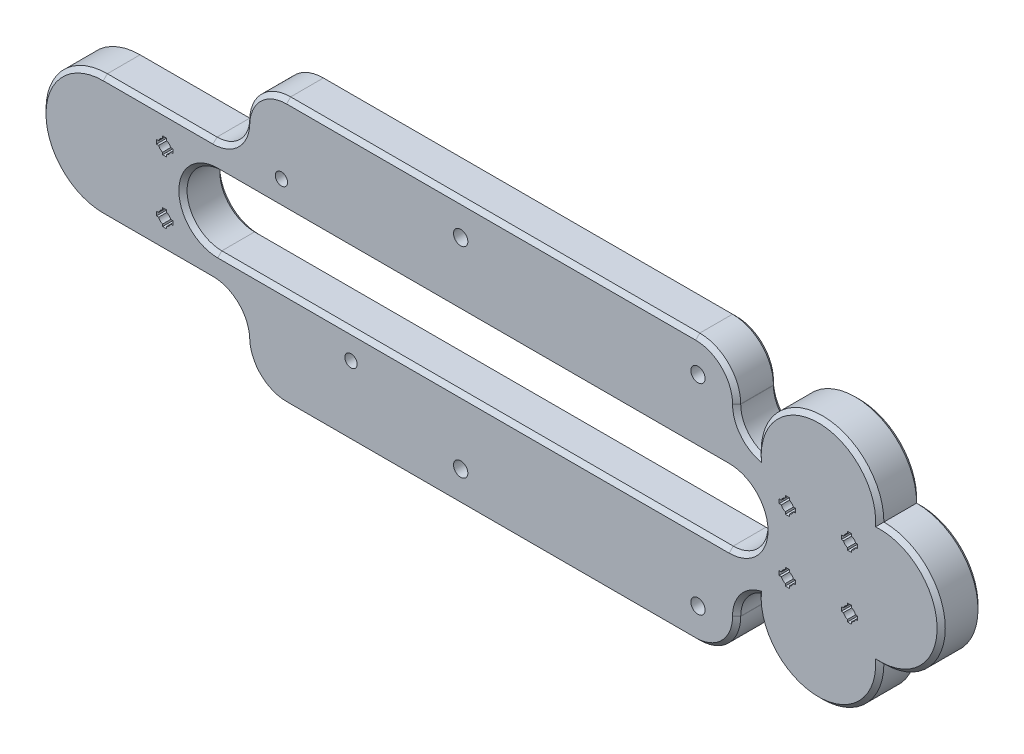
SolidWorks part; units mm, degrees
ref_plane "Front Plane" through (0, 0, 0) normal (0, 0, 1) x (1, 0, 0)
ref_plane "Top Plane" through (0, 0, 0) normal (0, 1, 0) x (1, 0, 0)
ref_plane "Right Plane" through (0, 0, 0) normal (1, 0, 0) x (0, 0, -1)
sketch "Sketch1" plane through (0, 0, 0) normal (0, 0, 1) x (1, 0, 0)
  line L0 (50.5551, 24.5) -> (50.5551, -24.5) construction
  line L1 (-50, -32.5) -> (50, -32.5)
  line L2 (-60, -22.5) -> (-60, 22.5)
  line L3 (-50, 32.5) -> (50, 32.5)
  line L4 (60, -22.5) -> (60, 22.5)
  line L5 (-60, -32.5) -> (60, 32.5) construction
  line L6 (-60, 32.5) -> (60, -32.5) construction
  line L7 (44.9072, 0) -> (118.6549, 0) construction
  line L8 (80, 17.2794) -> (80, -5.6936) construction
  line L9 (87.1, 5.6) -> (88.1, 5.6)
  line L10 (87.1, 5.6) -> (87.1, 6.1329)
  line L11 (87.1, 9.6) -> (88.1, 9.6)
  line L12 (88.1, 5.6) -> (88.1, 6.1329)
  line L13 (87.1, 5.6) -> (88.1, 9.6) construction
  line L14 (87.1, 9.6) -> (88.1, 5.6) construction
  line L15 (85.6, 7.1) -> (86.1329, 7.1)
  line L16 (85.6, 7.1) -> (85.6, 8.1)
  line L17 (85.6, 8.1) -> (86.1329, 8.1)
  line L18 (89.6, 7.1) -> (89.6, 8.1)
  line L19 (85.6, 7.1) -> (89.6, 8.1) construction
  line L20 (85.6, 8.1) -> (89.6, 7.1) construction
  line L21 (88.1, 9.0671) -> (88.1, 9.6)
  line L22 (89.0671, 8.1) -> (89.6, 8.1)
  line L23 (87.1, 9.0671) -> (87.1, 9.6)
  line L24 (89.0671, 7.1) -> (89.6, 7.1)
  line L25 (74.4, 7.1) -> (74.4, 8.1)
  line L26 (74.4, 8.1) -> (73.8671, 8.1)
  line L27 (72.9, 9.0671) -> (72.9, 9.6)
  line L28 (72.9, 9.6) -> (71.9, 9.6)
  line L29 (71.9, 9.0671) -> (71.9, 9.6)
  line L30 (70.9329, 8.1) -> (70.4, 8.1)
  line L31 (70.4, 7.1) -> (70.4, 8.1)
  line L32 (70.9329, 7.1) -> (70.4, 7.1)
  line L33 (71.9, 5.6) -> (71.9, 6.1329)
  line L34 (72.9, 5.6) -> (71.9, 5.6)
  line L35 (72.9, 5.6) -> (72.9, 6.1329)
  line L36 (74.4, 7.1) -> (73.8671, 7.1)
  line L37 (74.4, -7.1) -> (73.8671, -7.1)
  line L38 (72.9, -5.6) -> (72.9, -6.1329)
  line L39 (72.9, -5.6) -> (71.9, -5.6)
  line L40 (71.9, -5.6) -> (71.9, -6.1329)
  line L41 (70.9329, -7.1) -> (70.4, -7.1)
  line L42 (70.4, -7.1) -> (70.4, -8.1)
  line L43 (70.9329, -8.1) -> (70.4, -8.1)
  line L44 (71.9, -9.0671) -> (71.9, -9.6)
  line L45 (72.9, -9.6) -> (71.9, -9.6)
  line L46 (72.9, -9.0671) -> (72.9, -9.6)
  line L47 (74.4, -8.1) -> (73.8671, -8.1)
  line L48 (74.4, -7.1) -> (74.4, -8.1)
  line L49 (85.6, -7.1) -> (85.6, -8.1)
  line L50 (85.6, -8.1) -> (86.1329, -8.1)
  line L51 (87.1, -9.0671) -> (87.1, -9.6)
  line L52 (87.1, -9.6) -> (88.1, -9.6)
  line L53 (88.1, -9.0671) -> (88.1, -9.6)
  line L54 (89.0671, -8.1) -> (89.6, -8.1)
  line L55 (89.6, -7.1) -> (89.6, -8.1)
  line L56 (89.0671, -7.1) -> (89.6, -7.1)
  line L57 (88.1, -5.6) -> (88.1, -6.1329)
  line L58 (87.1, -5.6) -> (88.1, -5.6)
  line L59 (87.1, -5.6) -> (87.1, -6.1329)
  line L60 (85.6, -7.1) -> (86.1329, -7.1)
  line L61 (65, -15) -> (95, -15)
  line L62 (65, -15) -> (65, 15)
  line L63 (65, 15) -> (95, 15)
  line L64 (95, -15) -> (95, 15)
  line L65 (65, -15) -> (95, 15) construction
  line L66 (65, 15) -> (95, -15) construction
  line L67 (-80.3, 5.6) -> (-79.3, 5.6)
  line L68 (-80.3, 5.6) -> (-80.3, 6.1329)
  line L69 (-80.3, 9.6) -> (-79.3, 9.6)
  line L70 (-79.3, 5.6) -> (-79.3, 6.1329)
  line L71 (-81.8, 7.1) -> (-81.2671, 7.1)
  line L72 (-81.8, 7.1) -> (-81.8, 8.1)
  line L73 (-81.8, 8.1) -> (-81.2671, 8.1)
  line L74 (-77.8, 7.1) -> (-77.8, 8.1)
  line L75 (-79.3, 9.0671) -> (-79.3, 9.6)
  line L76 (-78.3329, 8.1) -> (-77.8, 8.1)
  line L77 (-80.3, 9.0671) -> (-80.3, 9.6)
  line L78 (-78.3329, 7.1) -> (-77.8, 7.1)
  line L79 (-81.8, -7.1) -> (-81.8, -8.1)
  line L80 (-81.8, -8.1) -> (-81.2671, -8.1)
  line L81 (-80.3, -9.0671) -> (-80.3, -9.6)
  line L82 (-80.3, -9.6) -> (-79.3, -9.6)
  line L83 (-79.3, -9.0671) -> (-79.3, -9.6)
  line L84 (-78.3329, -8.1) -> (-77.8, -8.1)
  line L85 (-77.8, -7.1) -> (-77.8, -8.1)
  line L86 (-78.3329, -7.1) -> (-77.8, -7.1)
  line L87 (-79.3, -5.6) -> (-79.3, -6.1329)
  line L88 (-80.3, -5.6) -> (-79.3, -5.6)
  line L89 (-80.3, -5.6) -> (-80.3, -6.1329)
  line L90 (-81.8, -7.1) -> (-81.2671, -7.1)
  line L91 (-79.8, 7.6) -> (-79.8, -7.6) construction
  line L92 (-64.8, 15) -> (-60, 15)
  line L93 (-94.8, -15) -> (-64.8, -15)
  line L94 (-94.8, -15) -> (-94.8, 15)
  line L95 (-94.8, 15) -> (-64.8, 15)
  line L96 (-64.8, -15) -> (-64.8, 15)
  line L97 (-94.8, -15) -> (-64.8, 15) construction
  line L98 (-94.8, 15) -> (-64.8, -15) construction
  line L99 (-64.8, -15) -> (-60, -15)
  line L100 (65, 15) -> (60, 15)
  line L101 (65, -15) -> (60, -15)
  arc A2 (87.1, 9.0671) -> (86.1329, 8.1) centre (87.6, 7.6) ccw
  arc A3 (86.1329, 7.1) -> (87.1, 6.1329) centre (87.6, 7.6) ccw
  arc A4 (89.0671, 8.1) -> (88.1, 9.0671) centre (87.6, 7.6) ccw
  arc A5 (88.1, 6.1329) -> (89.0671, 7.1) centre (87.6, 7.6) ccw
  arc A6 (72.9, 9.0671) -> (73.8671, 8.1) centre (72.4, 7.6) cw
  arc A7 (70.9329, 8.1) -> (71.9, 9.0671) centre (72.4, 7.6) cw
  arc A8 (71.9, 6.1329) -> (70.9329, 7.1) centre (72.4, 7.6) cw
  arc A9 (73.8671, 7.1) -> (72.9, 6.1329) centre (72.4, 7.6) cw
  arc A10 (73.8671, -7.1) -> (72.9, -6.1329) centre (72.4, -7.6) ccw
  arc A11 (71.9, -6.1329) -> (70.9329, -7.1) centre (72.4, -7.6) ccw
  arc A12 (70.9329, -8.1) -> (71.9, -9.0671) centre (72.4, -7.6) ccw
  arc A13 (72.9, -9.0671) -> (73.8671, -8.1) centre (72.4, -7.6) ccw
  arc A14 (87.1, -9.0671) -> (86.1329, -8.1) centre (87.6, -7.6) cw
  arc A15 (89.0671, -8.1) -> (88.1, -9.0671) centre (87.6, -7.6) cw
  arc A16 (88.1, -6.1329) -> (89.0671, -7.1) centre (87.6, -7.6) cw
  arc A17 (86.1329, -7.1) -> (87.1, -6.1329) centre (87.6, -7.6) cw
  arc A18 (65, 15) -> (95, 15) centre (80, 15) cw
  arc A19 (95, 15) -> (95, -15) centre (95, 0) cw
  arc A20 (95, -15) -> (65, -15) centre (80, -15) cw
  arc A21 (-80.3, 9.0671) -> (-81.2671, 8.1) centre (-79.8, 7.6) ccw
  arc A22 (-81.2671, 7.1) -> (-80.3, 6.1329) centre (-79.8, 7.6) ccw
  arc A23 (-78.3329, 8.1) -> (-79.3, 9.0671) centre (-79.8, 7.6) ccw
  arc A24 (-79.3, 6.1329) -> (-78.3329, 7.1) centre (-79.8, 7.6) ccw
  arc A25 (-80.3, -9.0671) -> (-81.2671, -8.1) centre (-79.8, -7.6) cw
  arc A26 (-78.3329, -8.1) -> (-79.3, -9.0671) centre (-79.8, -7.6) cw
  arc A27 (-79.3, -6.1329) -> (-78.3329, -7.1) centre (-79.8, -7.6) cw
  arc A28 (-81.2671, -7.1) -> (-80.3, -6.1329) centre (-79.8, -7.6) cw
  arc A29 (-94.8, 15) -> (-94.8, -15) centre (-94.8, 0) ccw
  circle A30 centre (-7.4449, 24.5) radius 1.75
  circle A31 centre (-7.4449, -24.5) radius 1.75
  circle A32 centre (50.5551, 24.5) radius 1.75
  circle A33 centre (50.5551, -24.5) radius 1.75
  circle A34 centre (-51.2532, 15) radius 1.5
  circle A35 centre (-34.2532, -15) radius 1.5
  arc A36 (50, 32.5) -> (60, 22.5) centre (50, 22.5) cw
  arc A37 (50, -32.5) -> (60, -22.5) centre (50, -22.5) ccw
  arc A38 (-50, -32.5) -> (-60, -22.5) centre (-50, -22.5) cw
  arc A39 (-60, 22.5) -> (-50, 32.5) centre (-50, 22.5) cw
  point P5 (0, 0)
  point P83 (80, 0)
  point P90 (-79.8, 0)
  point P128 (-79.8, 0)
  point P139 (50.5551, 0)
  point P141 (-39.1601, -15)
  point P142 (-36.4074, -15)
  point P144 (-34.2532, -15)
  dimension "D2" = 3.5
  dimension "D15" = 3
  dimension "D18" = 10
  dimension "D3" = 65
  dimension "D4" = 120
  dimension "D5" = 30
  dimension "D6" = 30
  dimension "D7" = 152.2
  dimension "D8" = 80
  dimension "D9" = 7.6
  dimension "D10" = 15.2
  dimension "D11" = 7.6
  dimension "D12" = 15.2
  dimension "D13" = 49
  dimension "D14" = 58
  dimension "D16" = 30
  dimension "D17" = 17
extrude "Boss-Extrude1" add sketch "Sketch1" along normal blind 10 contours L94 A29 | L93 L96 L95 L94 A24 L70 L67 L68 A22 L71 L72 L73 A21 L77 L69 L75 A23 L76 L74 L78 L90 A28 L89 L88 L87 A27 L86 L85 L84 A26 L83 L82 L81 A25 L80 L79 | L96 L99 L2 L92 | L1 L4 L3 L2 A35 A34 A33 A32 A31 A30 | L101 L62 L100 L4 | L61 L64 L63 L62 A13 L46 L45 L44 A12 L43 L42 L41 A11 L40 L39 L38 A10 L37 L48 L47 A5 L12 L9 L10 A3 L15 L16 L17 A2 L23 L11 L21 A4 L22 L18 L24 L36 A9 L35 L34 L33 A8 L32 L31 L30 A7 L29 L28 | A18 L63 | A19 L64 | A20 L61
fillet "Fillet2" radius 8 4 edges at (60, 15, 5) (60, -15, 5) (-60, -15, 5) (-60, 15, 5)
chamfer "Chamfer1" distance 1 angle 45 36 edges at (-81.3965, 15, 10) (-81.3965, 15, 0) (-109.8, 0, 0) (-109.8, 0, 10) (0, 32.5, 0) (0, 32.5, 10) (80, 30, 0) (80, 30, 10) (110, 0, 0) (110, 0, 10) (80, -30, 0) (80, -30, 10) (0, -32.5, 0) (0, -32.5, 10) (-81.3965, -15, 0) (-81.3965, -15, 10) (61.3668, 17.9441, 10) (61.3668, 17.9441, 0) (61.3668, -17.9441, 10) (61.3668, -17.9441, 0) (-62.4153, 17.2651, 10) (-62.4153, 17.2651, 0) (-62.4153, -17.2651, 10) (-62.4153, -17.2651, 0) (60, 22.4581, 10) (60, 22.4581, 0) (60, -22.4581, 10) (60, -22.4581, 0) (57.0711, 29.5711, 0) (57.0711, 29.5711, 10) (57.0711, -29.5711, 0) (57.0711, -29.5711, 10) (-56.9722, 29.6686, 0) (-56.9722, 29.6686, 10) (-56.9722, -29.6686, 10) (-56.9722, -29.6686, 0)
sketch "Sketch3" plane through (0, 0, 10) normal (0, 0, 1) x (1, 0, 0)
  line L0 (-66.8236, 0) -> (58.1764, 0) construction
  line L1 (-66.8236, 8.5) -> (58.1764, 8.5)
  line L2 (-66.8236, -8.5) -> (58.1764, -8.5)
  line L3 (-41.588, 14) -> (-41.588, -14) construction
  line L4 (-67.9931, 14) -> (-94.8, 14) construction
  line L5 (-94.8, -14) -> (-67.9931, -14) construction
  arc A0 (-66.8236, 8.5) -> (-66.8236, -8.5) centre (-66.8236, 0) ccw
  arc A1 (58.1764, -8.5) -> (58.1764, 8.5) centre (58.1764, 0) ccw
  point P2 (-4.3236, 0)
  point P13 (-41.588, 0)
  point P14 (54.322, 0)
  point P15 (-66.8236, 0)
  dimension "D1" = 17
  dimension "D2" = 125
extrude "Cut-Extrude2" cut sketch "Sketch3" against normal through all
chamfer "Chamfer2" distance 1 angle 45 8 edges at (-75.3236, 0, 10) (-75.3236, 0, 0) (66.6764, 0, 10) (66.6764, 0, 0) (-4.3236, -8.5, 10) (-4.3236, -8.5, 0) (-4.3236, 8.5, 10) (-4.3236, 8.5, 0)
